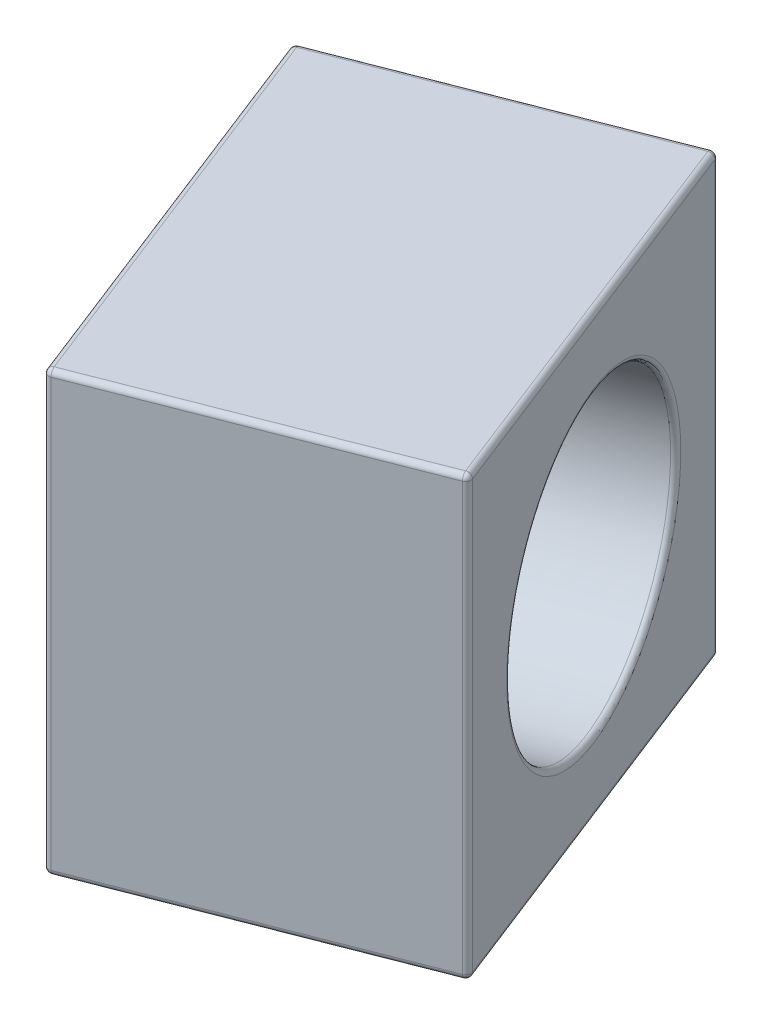
SolidWorks part; units mm, degrees
ref_plane "Front Plane" through (0, 0, 0) normal (0, 0, 1) x (1, 0, 0)
ref_plane "Top Plane" through (0, 0, 0) normal (0, 1, 0) x (1, 0, 0)
ref_plane "Right Plane" through (0, 0, 0) normal (1, 0, 0) x (0, 0, -1)
sketch "Sketch1" plane through (0, 0, 0) normal (0, 1, 0) x (1, 0, 0)
  line L0 (0, 0) -> (640, 0) construction
  line L1 (0, 0) -> (591.2829, 244.9174)
  line L2 (0, 0) -> (591.2829, -244.9174)
  line L3 (0, 0) -> (244.9174, -591.2829)
  line L4 (0, 0) -> (-244.9174, -591.2829)
  line L5 (0, 0) -> (-591.2829, -244.9174)
  line L6 (0, 0) -> (-591.2829, 244.9174)
  line L7 (0, 0) -> (-244.9174, 591.2829)
  line L8 (0, 0) -> (244.9174, 591.2829)
  line L9 (0, 145) -> (55, 145) construction
  line L10 (0, 0) -> (100, 0) construction
  line L11 (0, 0) -> (0, 145) construction
  line L14 (100, 0) -> (100, 145) construction
  circle A0 centre (0, 0) radius 640 construction
  point P15 (0, 0)
  dimension "D1" = 1280
  dimension "D2" = 22.5
  dimension "D4" = 145
  dimension "D5" = 100
  dimension "D6" = 55
  dimension "D3" = 8
sketch "Sketch2" plane through (0, 0, 0) normal (0, 1, 0) x (1, 0, 0)
  line L0 (-486.9956, 169.5033) -> (-66.9956, 169.5033) construction
  line L1 (-188.7141, -86.1278) -> (-188.7141, 241.8722) construction
  line L2 (525.6625, -1048.8053) -> (466.9027, -726.1115) construction
sketch "Sketch3" plane through (0, 0, 0) normal (0, 1, 0) x (1, 0, 0)
  line L0 (0, 0) -> (381.2468, 0) construction
  line L5 (0, 0) -> (0, 199.4415) construction
  line L6 (-10.2736, 158.9263) -> (10.2736, 158.9263)
  line L7 (10.2736, 158.9263) -> (13.1995, 163.9003)
  line L8 (13.1995, 163.9003) -> (45.5131, 148.2994)
  line L9 (45.5131, 148.2994) -> (66.2904, 80.9335)
  line L10 (66.2904, 80.9335) -> (73.8622, 80.9335)
  line L11 (73.8622, 80.9335) -> (86.8684, 42.4396)
  line L12 (86.8684, 42.4396) -> (86.8684, 30.0712)
  line L13 (86.8684, 30.0712) -> (81.3965, 24.5993)
  line L14 (81.3965, 24.5993) -> (81.3965, -24.5993)
  line L15 (-5.8349, 67.4929) -> (5.8349, 67.4929) construction
  line L16 (16.6008, 64.1674) -> (16.6008, 27.6557) construction
  line L17 (16.6008, 27.6557) -> (13.2646, 22.809) construction
  line L18 (13.2646, 22.809) -> (13.2646, -22.809) construction
  line L19 (5.8349, 128.0146) -> (5.8349, 107.4452)
  line L22 (5.8349, 107.4452) -> (9.2702, 107.4452)
  line L25 (9.2702, 107.4452) -> (10.663, 103.7163)
  line L26 (10.663, 103.7163) -> (20.7578, 101.0699)
  line L27 (20.7578, 101.0699) -> (32.199, 111.7601)
  line L28 (32.199, 111.7601) -> (32.199, 123.5038)
  line L29 (32.199, 123.5038) -> (24.9078, 123.5038)
  line L30 (24.9078, 123.5038) -> (13.8412, 132.5856)
  line L31 (13.8412, 132.5856) -> (9.2702, 132.5856)
  line L32 (9.2702, 132.5856) -> (5.8349, 128.0146)
  line L33 (41.9414, 39.7891) -> (51.4866, 54.1602)
  line L34 (51.4866, 54.1602) -> (55.4027, 54.1602)
  line L35 (55.4027, 54.1602) -> (58.1637, 51.3993)
  line L36 (58.1637, 51.3993) -> (58.1637, 43.1872)
  line L37 (58.1637, 43.1872) -> (66.3555, 28.462)
  line L38 (66.3555, 28.462) -> (66.3555, 24.0728)
  line L39 (66.3555, 24.0728) -> (62.2596, 17.9061)
  line L40 (62.2596, 17.9061) -> (47.8497, 18.1669)
  line L41 (47.8497, 18.1669) -> (41.9414, 27.1878)
  line L42 (41.9414, 27.1878) -> (41.9414, 39.7891)
  line L43 (-41.9414, 27.1878) -> (-41.9414, 39.7891)
  line L44 (-47.8497, 18.1669) -> (-41.9414, 27.1878)
  line L45 (-62.2596, 17.9061) -> (-47.8497, 18.1669)
  line L46 (-66.3555, 24.0728) -> (-62.2596, 17.9061)
  line L47 (-66.3555, 28.462) -> (-66.3555, 24.0728)
  line L48 (-58.1637, 43.1872) -> (-66.3555, 28.462)
  line L49 (-58.1637, 51.3993) -> (-58.1637, 43.1872)
  line L50 (-55.4027, 54.1602) -> (-58.1637, 51.3993)
  line L51 (-51.4866, 54.1602) -> (-55.4027, 54.1602)
  line L52 (-41.9414, 39.7891) -> (-51.4866, 54.1602)
  line L53 (-9.2702, 132.5856) -> (-5.8349, 128.0146)
  line L54 (-13.8412, 132.5856) -> (-9.2702, 132.5856)
  line L55 (-24.9078, 123.5038) -> (-13.8412, 132.5856)
  line L56 (-32.199, 123.5038) -> (-24.9078, 123.5038)
  line L57 (-32.199, 111.7601) -> (-32.199, 123.5038)
  line L58 (-20.7578, 101.0699) -> (-32.199, 111.7601)
  line L59 (-10.663, 103.7163) -> (-20.7578, 101.0699)
  line L60 (-9.2702, 107.4452) -> (-10.663, 103.7163)
  line L61 (-5.8349, 107.4452) -> (-9.2702, 107.4452)
  line L62 (-5.8349, 128.0146) -> (-5.8349, 107.4452)
  line L63 (-13.2646, 22.809) -> (-13.2646, -22.809) construction
  line L64 (-16.6008, 27.6557) -> (-13.2646, 22.809) construction
  line L65 (-16.6008, 64.1674) -> (-16.6008, 27.6557) construction
  line L66 (-81.3965, 24.5993) -> (-81.3965, -24.5993)
  line L67 (-86.8684, 30.0712) -> (-81.3965, 24.5993)
  line L68 (-86.8684, 42.4396) -> (-86.8684, 30.0712)
  line L69 (-73.8622, 80.9335) -> (-86.8684, 42.4396)
  line L70 (-66.2904, 80.9335) -> (-73.8622, 80.9335)
  line L71 (-45.5131, 148.2994) -> (-66.2904, 80.9335)
  line L72 (-13.1995, 163.9003) -> (-45.5131, 148.2994)
  line L73 (-10.2736, 158.9263) -> (-13.1995, 163.9003)
  line L74 (-10.2736, -158.9263) -> (-13.1995, -163.9003)
  line L75 (-13.1995, -163.9003) -> (-45.5131, -148.2994)
  line L76 (-45.5131, -148.2994) -> (-66.2904, -80.9335)
  line L77 (-66.2904, -80.9335) -> (-73.8622, -80.9335)
  line L78 (-73.8622, -80.9335) -> (-86.8684, -42.4396)
  line L79 (-86.8684, -42.4396) -> (-86.8684, -30.0712)
  line L80 (-86.8684, -30.0712) -> (-81.3965, -24.5993)
  line L81 (-16.6008, -64.1674) -> (-16.6008, -27.6557) construction
  line L82 (-16.6008, -27.6557) -> (-13.2646, -22.809) construction
  line L83 (-5.8349, -128.0146) -> (-5.8349, -107.4452)
  line L84 (-5.8349, -107.4452) -> (-9.2702, -107.4452)
  line L85 (-9.2702, -107.4452) -> (-10.663, -103.7163)
  line L86 (-10.663, -103.7163) -> (-20.7578, -101.0699)
  line L87 (-20.7578, -101.0699) -> (-32.199, -111.7601)
  line L88 (-32.199, -111.7601) -> (-32.199, -123.5038)
  line L89 (-32.199, -123.5038) -> (-24.9078, -123.5038)
  line L90 (-24.9078, -123.5038) -> (-13.8412, -132.5856)
  line L91 (-13.8412, -132.5856) -> (-9.2702, -132.5856)
  line L92 (-9.2702, -132.5856) -> (-5.8349, -128.0146)
  line L93 (-41.9414, -39.7891) -> (-51.4866, -54.1602)
  line L94 (-51.4866, -54.1602) -> (-55.4027, -54.1602)
  line L95 (-55.4027, -54.1602) -> (-58.1637, -51.3993)
  line L96 (-58.1637, -51.3993) -> (-58.1637, -43.1872)
  line L97 (-58.1637, -43.1872) -> (-66.3555, -28.462)
  line L98 (-66.3555, -28.462) -> (-66.3555, -24.0728)
  line L99 (-66.3555, -24.0728) -> (-62.2596, -17.9061)
  line L100 (-62.2596, -17.9061) -> (-47.8497, -18.1669)
  line L101 (-47.8497, -18.1669) -> (-41.9414, -27.1878)
  line L102 (-41.9414, -27.1878) -> (-41.9414, -39.7891)
  line L103 (41.9414, -27.1878) -> (41.9414, -39.7891)
  line L104 (47.8497, -18.1669) -> (41.9414, -27.1878)
  line L105 (62.2596, -17.9061) -> (47.8497, -18.1669)
  line L106 (66.3555, -24.0728) -> (62.2596, -17.9061)
  line L107 (66.3555, -28.462) -> (66.3555, -24.0728)
  line L108 (58.1637, -43.1872) -> (66.3555, -28.462)
  line L109 (58.1637, -51.3993) -> (58.1637, -43.1872)
  line L110 (55.4027, -54.1602) -> (58.1637, -51.3993)
  line L111 (51.4866, -54.1602) -> (55.4027, -54.1602)
  line L112 (41.9414, -39.7891) -> (51.4866, -54.1602)
  line L113 (9.2702, -132.5856) -> (5.8349, -128.0146)
  line L114 (13.8412, -132.5856) -> (9.2702, -132.5856)
  line L115 (24.9078, -123.5038) -> (13.8412, -132.5856)
  line L116 (32.199, -123.5038) -> (24.9078, -123.5038)
  line L117 (32.199, -111.7601) -> (32.199, -123.5038)
  line L118 (20.7578, -101.0699) -> (32.199, -111.7601)
  line L119 (10.663, -103.7163) -> (20.7578, -101.0699)
  line L120 (9.2702, -107.4452) -> (10.663, -103.7163)
  line L121 (5.8349, -107.4452) -> (9.2702, -107.4452)
  line L122 (5.8349, -128.0146) -> (5.8349, -107.4452)
  line L123 (16.6008, -27.6557) -> (13.2646, -22.809) construction
  line L124 (16.6008, -64.1674) -> (16.6008, -27.6557) construction
  line L125 (-5.8349, -67.4929) -> (5.8349, -67.4929) construction
  line L126 (86.8684, -30.0712) -> (81.3965, -24.5993)
  line L127 (86.8684, -42.4396) -> (86.8684, -30.0712)
  line L128 (73.8622, -80.9335) -> (86.8684, -42.4396)
  line L129 (66.2904, -80.9335) -> (73.8622, -80.9335)
  line L130 (45.5131, -148.2994) -> (66.2904, -80.9335)
  line L131 (13.1995, -163.9003) -> (45.5131, -148.2994)
  line L132 (10.2736, -158.9263) -> (13.1995, -163.9003)
  line L133 (-10.2736, -158.9263) -> (10.2736, -158.9263)
  line L134 (-5.3457, 68.4929) -> (5.3457, 68.4929)
  line L135 (17.6008, 64.1674) -> (17.6008, 27.3448)
  line L136 (17.6008, 27.3448) -> (14.2646, 22.498)
  line L137 (14.2646, 22.498) -> (14.2646, -22.498)
  line L138 (-17.6008, 64.1674) -> (-17.6008, 27.3448)
  line L139 (-17.6008, 27.3448) -> (-14.2646, 22.498)
  line L140 (-5.3457, 68.4929) -> (5.3457, 68.4929) construction
  line L141 (14.2646, 22.498) -> (14.2646, -22.498) construction
  line L142 (17.6008, -27.3448) -> (14.2646, -22.498) construction
  line L143 (17.6008, -64.1674) -> (17.6008, -27.3448) construction
  line L144 (-14.2646, 22.498) -> (-14.2646, -22.498)
  line L145 (17.6008, -64.1674) -> (17.6008, -27.3448)
  line L146 (17.6008, -27.3448) -> (14.2646, -22.498)
  line L147 (-17.6008, -27.3448) -> (-14.2646, -22.498)
  line L148 (-17.6008, -64.1674) -> (-17.6008, -27.3448)
  line L149 (-5.3457, -68.4929) -> (5.3457, -68.4929)
  arc A0 (5.8349, 67.4929) -> (16.6008, 64.0252) centre (10.663, 64.0364) cw construction
  arc A5 (-5.8349, 67.4929) -> (-16.6008, 64.0252) centre (-10.663, 64.0364) ccw construction
  arc A6 (-5.8349, -67.4929) -> (-16.6008, -64.0252) centre (-10.663, -64.0364) cw construction
  arc A7 (5.8349, -67.4929) -> (16.6008, -64.0252) centre (10.663, -64.0364) ccw construction
  arc A8 (-5.3457, 68.4929) -> (-17.6008, 64.0234) centre (-10.663, 64.0364) ccw
  arc A9 (5.3457, 68.4929) -> (17.6008, 64.0234) centre (10.663, 64.0364) cw
  arc A10 (-5.3457, 68.4929) -> (-17.6008, 64.0234) centre (-10.663, 64.0364) ccw construction
  arc A11 (5.3457, -68.4929) -> (17.6008, -64.0234) centre (10.663, -64.0364) ccw
  arc A12 (-5.3457, -68.4929) -> (-17.6008, -64.0234) centre (-10.663, -64.0364) cw
  ellipse E0 centre (11.3851, 149.6854) end of major axis (12.0553, 155.2702) minor radius 3.0047
  ellipse E1 centre (33.6925, 82.363) end of major axis (41.1096, 88.3895) minor radius 4.3287
  ellipse E2 centre (44.8955, 74.0187) end of major axis (51.4866, 79.374) minor radius 4.6847
  ellipse E3 centre (66.3555, 66.447) end of major axis (67.1471, 72.2416) minor radius 3.5711
  ellipse E4 centre (-66.3555, 66.447) end of major axis (-67.1471, 72.2416) minor radius 3.5711
  ellipse E5 centre (-44.8955, 74.0187) end of major axis (-51.4866, 79.374) minor radius 4.6847
  ellipse E6 centre (-33.6925, 82.363) end of major axis (-41.1096, 88.3895) minor radius 4.3287
  ellipse E7 centre (-11.3851, 149.6854) end of major axis (-12.0553, 155.2702) minor radius 3.0047
  ellipse E8 centre (-11.3851, -149.6854) end of major axis (-12.0553, -155.2702) minor radius 3.0047
  ellipse E9 centre (-33.6925, -82.363) end of major axis (-41.1096, -88.3895) minor radius 4.3287
  ellipse E10 centre (-44.8955, -74.0187) end of major axis (-51.4866, -79.374) minor radius 4.6847
  ellipse E11 centre (-66.3555, -66.447) end of major axis (-67.1471, -72.2416) minor radius 3.5711
  ellipse E12 centre (66.3555, -66.447) end of major axis (67.1471, -72.2416) minor radius 3.5711
  ellipse E13 centre (44.8955, -74.0187) end of major axis (51.4866, -79.374) minor radius 4.6847
  ellipse E14 centre (33.6925, -82.363) end of major axis (41.1096, -88.3895) minor radius 4.3287
  ellipse E15 centre (11.3851, -149.6854) end of major axis (12.0553, -155.2702) minor radius 3.0047
  point P117 (0, 67.4929)
  point P126 (0, 158.9263)
  point P180 (0, -158.9263)
  point P181 (0, -67.4929)
  point P190 (-81.3965, 0)
  point P193 (-13.2646, 0)
  point P234 (13.2646, 0)
  point P237 (81.3965, 0)
  point P261 (0, 68.4929)
  point P271 (14.2646, 0)
  point P274 (-14.2646, 0)
  dimension "D1" = 1
sketch "Sketch4" plane through (0, 0, 0) normal (0, 1, 0) x (1, 0, 0)
  line L0 (0, 0) -> (81.2255, 0) construction
  line L1 (0, 0) -> (0, 97.3086) construction
  line L2 (0, 0) -> (0, 199.4415) construction
  line L3 (-10.1399, 86.6928) -> (10.1399, 86.6928)
  line L4 (10.1399, 86.6928) -> (16.0235, 80.8091)
  line L5 (16.0235, 80.8091) -> (23.9736, 57.3032)
  line L6 (23.9736, 57.3032) -> (23.9736, 47.8894)
  line L7 (23.9736, 47.8894) -> (21.6776, 47.8894)
  line L8 (21.6776, 47.8894) -> (21.6776, 27.2256)
  line L9 (21.6776, 27.2256) -> (27.5382, 22.1416)
  line L10 (27.5382, 22.1416) -> (27.5382, 14.9676)
  line L11 (27.5382, 14.9676) -> (23.9736, 10.8585)
  line L12 (23.9736, 10.8585) -> (23.9736, -10.8585)
  line L13 (-23.9736, 10.8585) -> (-23.9736, -10.8585)
  line L14 (-27.5382, 14.9676) -> (-23.9736, 10.8585)
  line L15 (-27.5382, 22.1416) -> (-27.5382, 14.9676)
  line L16 (-21.6776, 27.2256) -> (-27.5382, 22.1416)
  line L17 (-21.6776, 47.8894) -> (-21.6776, 27.2256)
  line L18 (-23.9736, 47.8894) -> (-21.6776, 47.8894)
  line L19 (-23.9736, 57.3032) -> (-23.9736, 47.8894)
  line L20 (-16.0235, 80.8091) -> (-23.9736, 57.3032)
  line L21 (-10.1399, 86.6928) -> (-16.0235, 80.8091)
  line L22 (-10.1399, -86.6928) -> (-16.0235, -80.8091)
  line L23 (-16.0235, -80.8091) -> (-23.9736, -57.3032)
  line L24 (-23.9736, -57.3032) -> (-23.9736, -47.8894)
  line L25 (-23.9736, -47.8894) -> (-21.6776, -47.8894)
  line L26 (-21.6776, -47.8894) -> (-21.6776, -27.2256)
  line L27 (-21.6776, -27.2256) -> (-27.5382, -22.1416)
  line L28 (-27.5382, -22.1416) -> (-27.5382, -14.9676)
  line L29 (-27.5382, -14.9676) -> (-23.9736, -10.8585)
  line L30 (27.5382, -14.9676) -> (23.9736, -10.8585)
  line L31 (27.5382, -22.1416) -> (27.5382, -14.9676)
  line L32 (21.6776, -27.2256) -> (27.5382, -22.1416)
  line L33 (21.6776, -47.8894) -> (21.6776, -27.2256)
  line L34 (23.9736, -47.8894) -> (21.6776, -47.8894)
  line L35 (23.9736, -57.3032) -> (23.9736, -47.8894)
  line L36 (16.0235, -80.8091) -> (23.9736, -57.3032)
  line L37 (10.1399, -86.6928) -> (16.0235, -80.8091)
  line L38 (-10.1399, -86.6928) -> (10.1399, -86.6928)
  point P3 (0, -86.6928)
  point P27 (0, 86.6928)
  point P37 (-23.9736, 0)
  point P38 (23.9736, 0)
sketch "Sketch5" plane through (0, 0, 0) normal (0, 1, 0) x (1, 0, 0)
  line L0 (0, 68.4929) -> (0, 86.6928) construction
  line L1 (15.4511, 110) -> (223.3697, 546.0887)
  line L2 (0, 0) -> (0, 251.8084) construction
  line L3 (0, 110) -> (47.9221, 110) construction
  line L5 (244.9174, 616.9519) -> (262.4572, 609.0616) construction
  line L6 (262.4572, 609.0616) -> (269.1565, 599.6825) construction
  line L7 (269.1565, 599.6825) -> (256.4381, 571.4103) construction
  line L8 (256.4381, 571.4103) -> (244.9174, 563.1812) construction
  line L9 (244.9174, 563.1812) -> (221.08, 517.0826) construction
  line L10 (221.08, 517.0826) -> (201.6817, 527.1134) construction
  line L11 (201.6817, 527.1134) -> (221.6088, 571.4103) construction
  line L12 (221.6088, 571.4103) -> (218.2415, 584.6462) construction
  line L13 (218.2415, 584.6462) -> (232.4366, 616.2011) construction
  line L14 (232.4366, 616.2011) -> (244.9174, 616.9519) construction
  line L15 (244.9174, 591.2829) -> (309.3694, 564.586) construction
  line L16 (269.6266, 526.9284) -> (173.6132, 566.6985) construction
  line L18 (0, 0) -> (107.3069, 0) construction
  dimension "D1" = 110
  dimension "D2" = 50
sketch "Sketch6" plane through (0, 0, 0) normal (0, 1, 0) x (1, 0, 0)
  line L1 (27.9119, 24.7148) -> (544.6401, 226.6863)
  circle A0 centre (0, 0) radius 640 construction
  circle A1 centre (0, 0) radius 640 construction
  circle A3 centre (0, 0) radius 589.9318 construction
  dimension "D1" = 50.0682
sketch "Sketch19" plane through (0, 0, 0) normal (0, 1, 0) x (1, 0, 0)
  line L0 (128.4599, 309.2664) -> (271.805, 137.4916)
  line L5 (26.7343, 104.6204) -> (234.6528, 540.7091)
  line L6 (26.7343, 104.6204) -> (234.6528, 540.7091) construction
  line L7 (4.1679, 115.3796) -> (212.0865, 551.4683)
  line L8 (4.1679, 115.3796) -> (212.0865, 551.4683) construction
  line L9 (20.631, 43.3425) -> (537.3592, 245.3139)
  line L10 (32.4624, 13.0726) -> (549.1907, 215.044)
  line L11 (32.4624, 13.0726) -> (549.1907, 215.044) construction
  line L12 (23.3613, 36.3571) -> (540.0895, 238.3286)
  line L13 (23.3613, 36.3571) -> (540.0895, 238.3286) construction
  line L14 (20.631, 43.3425) -> (537.3592, 245.3139) construction
  line L15 (30.1192, 103.0065) -> (238.0378, 539.0952)
  line L16 (30.1192, 103.0065) -> (238.0378, 539.0952) construction
  line L22 (21.9961, 39.8498) -> (538.7244, 241.8213)
  line L23 (21.9961, 39.8498) -> (538.7244, 241.8213) construction
  line L24 (33.5042, 101.3926) -> (241.4227, 537.4813)
  line L25 (33.5042, 101.3926) -> (241.4227, 537.4813) construction
  dimension "D1" = 12.5
  dimension "D2" = 12.5
  dimension "D3" = 12.5
  dimension "D4" = 12.5
  dimension "D5" = 16.25
  dimension "D8" = 16.25
  dimension "D10" = 20
  dimension "D11" = 20
sketch "Sketch20" plane through (0, 0, 0) normal (0, 1, 0) x (1, 0, 0)
  line L0 (27.9119, 24.7148) -> (544.6401, 226.6863) construction
  line L1 (27.9119, 24.7148) -> (544.6401, 226.6863) construction
  line L2 (271.0309, 98.2683) -> (298.9724, 109.1897)
  line L3 (256.4691, 135.5236) -> (284.4106, 146.4449)
  line L4 (298.9724, 109.1897) -> (284.4106, 146.4449)
  line L5 (285.0016, 103.729) -> (270.4398, 140.9843) construction
  line L6 (271.0309, 98.2683) -> (256.4691, 135.5236)
  line L7 (20.631, 43.3425) -> (537.3592, 245.3139) construction
  line L8 (35.1928, 6.0872) -> (551.921, 208.0587) construction
  dimension "D1" = 20
  dimension "D2" = 20
  dimension "D3" = 15
  dimension "D4" = 15
extrude "Boss-Extrude1" add sketch "Sketch20" along normal blind 20 and the other way blind 20
sweep "Cut-Sweep1" cut path "Sketch6" circular profile diameter 27 parameters "D3"=27
sweep "Cut-Sweep2" cut path "Sketch19" circular profile diameter 12 parameters "D3"=12
fillet "Fillet1" radius 0.5 15 edges at (291.6915, -20, -127.8173) (291.6915, 20, -127.8173) (285.0016, -20, -103.729) (285.0016, 20, -103.729) (298.9724, 0, -109.1897) (263.75, -20, -116.896) (263.75, 20, -116.896) (271.0309, 0, -98.2683) (268.6646, 0, -104.3223) (270.4398, -20, -140.9843) (284.4106, 0, -146.4449) (270.4398, 20, -140.9843) (256.4691, 0, -135.5236) (275.1641, 0, -142.8308) (286.7768, 0, -140.391)
